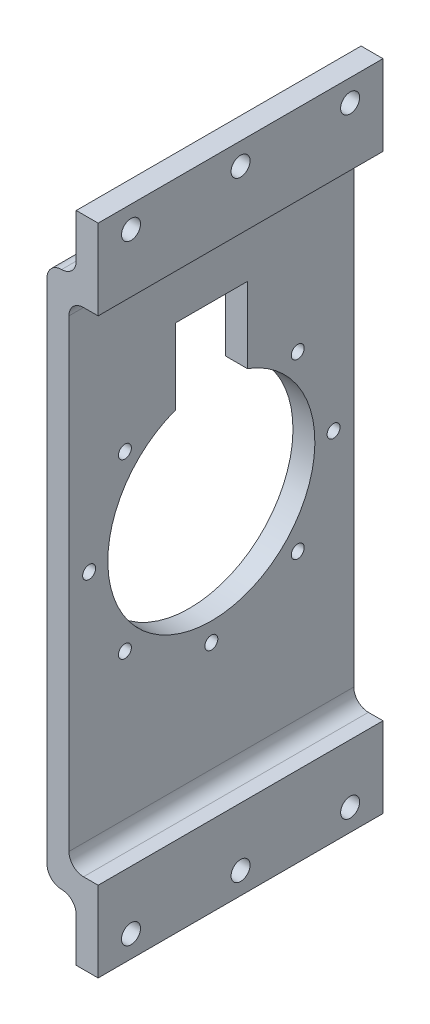
SolidWorks part; units mm, degrees
other "Markup1"
sketch "Sketch9" plane through (-7.62, -27.94, -49.53) normal (-1, 0, 0) x (0, 0, 1)
sketch "Sketch12" plane through (-7.62, -27.94, -49.53) normal (-1, 0, 0) x (0, 0, 1)
sketch "Sketch13" plane through (-7.62, -27.94, -49.53) normal (-1, 0, 0) x (0, 0, 1)
material "ABS"
ref_plane "Front Plane" through (0, 0, 0) normal (0, 0, 1) x (1, 0, 0)
ref_plane "Top Plane" through (0, 0, 0) normal (0, 1, 0) x (1, 0, 0)
ref_plane "Right Plane" through (0, 0, 0) normal (1, 0, 0) x (0, 0, -1)
sketch "Sketch1" plane through (0, 0, 0) normal (0, 0, 1) x (1, 0, 0)
  line L0 (0, 0) -> (0, 171.45)
  line L1 (0, 0) -> (10.16, 0)
  line L2 (-7.62, -7.62) -> (-7.62, 171.45)
  line L3 (-7.62, -7.62) -> (2.54, -7.62)
  line L5 (10.16, 0) -> (10.16, -7.62)
  line L8 (0, 171.45) -> (10.16, 171.45)
  line L9 (-7.62, 171.45) -> (-7.62, 179.07)
  line L10 (-7.62, 179.07) -> (2.54, 179.07)
  line L11 (10.16, 171.45) -> (10.16, 179.07)
  line L12 (10.16, -7.62) -> (10.16, -27.94)
  line L13 (10.16, -27.94) -> (2.54, -27.94)
  line L14 (2.54, -27.94) -> (2.54, -7.62)
  line L15 (10.16, 179.07) -> (10.16, 199.39)
  line L16 (-7.62, -7.62) -> (10.16, -7.62) construction
  line L17 (10.16, 199.39) -> (2.54, 199.39)
  line L18 (2.54, 199.39) -> (2.54, 179.07)
  dimension "D2" = 17.78
  dimension "D3" = 20.32
  dimension "D4" = 171.45
  dimension "D1" = 7.62
extrude "Boss-Extrude1" add sketch "Sketch1" along normal mid plane 99.06
ref_plane "Actuator Plane" through (0, 85.725, 0) normal (0, 1, 0) x (1, 0, 0)
fillet "Fillet1" radius 5.08 6 edges at (0, 0, 0) (2.54, -7.62, 0) (0, 171.45, 0) (2.54, 179.07, 0) (-7.62, 179.07, 0) (-7.62, -7.62, 0)
sketch "Sketch7" plane through (0, 0, 0) normal (1, 0, 0) x (0, 0, -1)
  line L0 (4.191, 85.725) -> (-4.191, 85.725) construction
  line L3 (-39.2649, 101.989) -> (0, 85.725) construction
  line L4 (0, 85.725) -> (-42.5, 85.725) construction
  circle A0 centre (0, 85.725) radius 42.5 construction
  circle A1 centre (-42.5, 85.725) radius 2.25
  circle A2 centre (-30.052, 115.777) radius 2.25
  circle A3 centre (0, 128.225) radius 2.25
  circle A4 centre (30.052, 115.777) radius 2.25
  circle A5 centre (42.5, 85.725) radius 2.25
  circle A6 centre (30.052, 55.673) radius 2.25
  circle A7 centre (0, 43.225) radius 2.25
  circle A8 centre (-30.052, 55.673) radius 2.25
  circle A9 centre (-39.2649, 101.989) radius 1.75 construction
  circle A10 centre (-16.264, 124.9899) radius 1.75 construction
  circle A11 centre (16.264, 124.9899) radius 1.75 construction
  circle A12 centre (39.2649, 101.989) radius 1.75 construction
  circle A13 centre (39.2649, 69.461) radius 1.75 construction
  circle A14 centre (16.264, 46.4601) radius 1.75 construction
  circle A15 centre (-16.264, 46.4601) radius 1.75 construction
  circle A16 centre (-39.2649, 69.461) radius 1.75 construction
  circle A17 centre (0, 85.725) radius 36
  point P28 (0, 85.725)
  point P45 (0, 85.725)
  dimension "D1" = 4.5
  dimension "D2" = 85
  dimension "D5" = 3.5
  dimension "D7" = 72
  dimension "D4" = 22.5
  dimension "D3" = 8
  dimension "D6" = 8
extrude "Cut-Extrude1" cut sketch "Sketch7" against normal up to surface (7.62 mm away) up to face at (-7.62, 85.725, 0)
sketch "Sketch8" plane through (2.54, 0, 0) normal (-1, 0, 0) x (0, 0, 1)
  line L0 (-38.1, 191.77) -> (0, 191.77) construction
  line L1 (0, 191.77) -> (38.1, 191.77) construction
  line L2 (0, -9.779) -> (0, 9.779) construction
  line L4 (-49.53, 199.39) -> (-49.53, 184.15) construction
  circle A0 centre (-38.1, 191.77) radius 3.302
  circle A1 centre (0, 191.77) radius 3.302
  circle A3 centre (38.1, 191.77) radius 3.302
  point P17 (-49.53, 191.77)
  dimension "D4" = 6.604
  dimension "D2" = 76.2
extrude "Cut-Extrude2" cut sketch "Sketch8" against normal up to surface (7.62 mm away) up to face at (10.16, 185.42, 0)
mirror "Mirror1" about plane through (0, 85.725, 0) normal (0, 1, 0) of "Cut-Extrude2"
sketch "Sketch14" plane through (-7.62, 0, 0) normal (-1, 0, 0) x (0, 0, 1)
  line L0 (12.5, 119.4852) -> (12.5, 145.725)
  line L1 (12.5, 145.725) -> (-12.5, 145.725)
  line L2 (-12.5, 145.725) -> (-12.5, 119.4852)
  circle A0 centre (0, 85.725) radius 36 construction
  arc A1 (12.5, 119.4852) -> (-12.5, 119.4852) centre (0, 85.725) ccw
  point P4 (0, 0)
  point P7 (-7.0034, 121.0372)
  point P8 (15.3194, 118.3029)
  point P9 (0, 0)
  point P10 (0, 145.725)
  dimension "D1" = 25
  dimension "D2" = 60
extrude "Cut-Extrude3" cut sketch "Sketch14" against normal up to surface (7.62 mm away) up to face at (0, 85.725, 40.25)
equation "\"VerticalHeight\"= 6.75"
equation "\"D4@Sketch1\"=\"VerticalHeight\""
